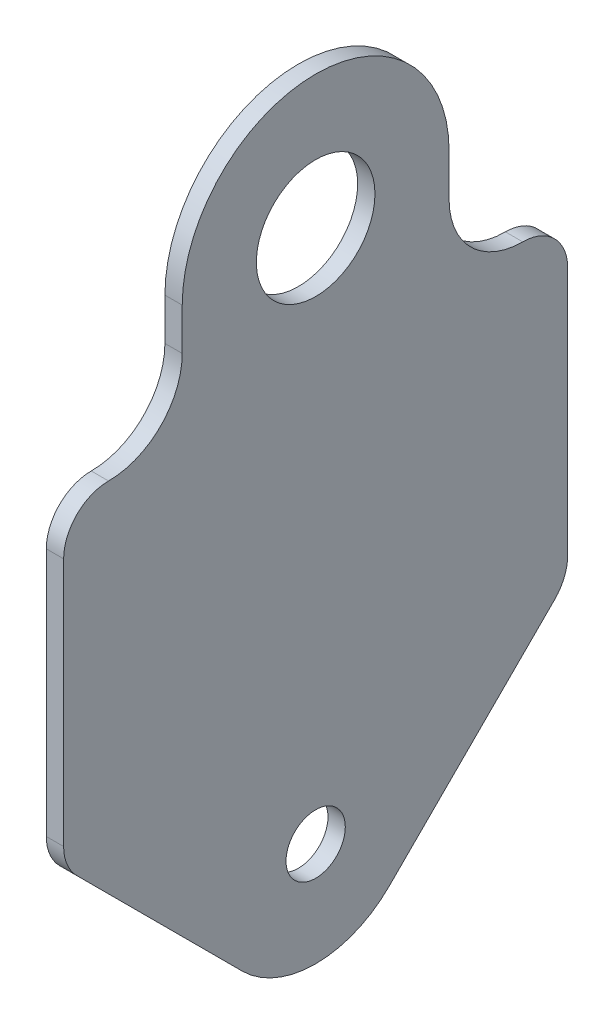
SolidWorks part; units mm, degrees
material "6061-T6 (SS)"
ref_plane "Front" through (0, 0, 0) normal (0, 0, 1) x (1, 0, 0)
ref_plane "Top" through (0, 0, 0) normal (0, 1, 0) x (1, 0, 0)
ref_plane "Right" through (0, 0, 0) normal (1, 0, 0) x (0, 0, -1)
ref_axis "side-side" through (80.9, 0, 0) along (-1, 0, 0)
ref_axis "up-down" through (0, 50, 0) along (0, -1, 0)
ref_axis "front-back" through (0, 0, -80.9) along (0, 0, 1)
sketch "Sketch1" plane through (0, 0, 0) normal (1, 0, 0) x (0, 0, -1)
  line L0 (0, 0) -> (-27.9363, -5.6405) construction
  line L1 (-18, 0) -> (18, 0) construction
  line L2 (-18, 0) -> (-18, -5.6405)
  line L4 (18, 0) -> (18, -5.6405)
  line L6 (-34, -21.6405) -> (-34, -55.2473)
  line L7 (-32.224, -59.535) -> (-9.8995, -81.8595)
  line L8 (0, -71.96) -> (0, -41.7737) construction
  line L9 (34, -21.6405) -> (34, -55.2473)
  line L10 (9.8995, -81.8595) -> (32.224, -59.535)
  line L12 (0, 50) -> (0, -50) construction
  arc A0 (-18, 0) -> (18, 0) centre (0, 0) cw
  circle A1 centre (0, 0) radius 8
  circle A2 centre (0, -71.96) radius 4
  arc A3 (-9.8995, -81.8595) -> (9.8995, -81.8595) centre (0, -71.96) ccw
  circle A4 centre (-27.9363, -5.6405) radius 7.48 construction
  arc A6 (0.5117, 28.4954) -> (-27.9363, -5.6405) centre (0, 0) ccw construction
  arc A8 (-27.9363, -15.5768) -> (-18, -5.6405) centre (-27.9363, -5.6405) ccw
  arc A9 (-27.9363, -15.5768) -> (-34, -21.6405) centre (-27.9363, -21.6405) ccw
  arc A10 (-34, -55.2473) -> (-32.224, -59.535) centre (-27.9363, -55.2473) ccw
  arc A11 (18, -5.6405) -> (27.9363, -15.5768) centre (27.9363, -5.6405) ccw
  arc A12 (27.9363, -15.5768) -> (34, -21.6405) centre (27.9363, -21.6405) cw
  arc A13 (34, -55.2473) -> (32.224, -59.535) centre (27.9363, -55.2473) cw
  circle A14 centre (-29.2625, -43.5) radius 1.3525 construction
  circle A15 centre (-29.2625, -32) radius 1.3525 construction
  dimension "D1" = 16
  dimension "D2" = 10
  dimension "D4" = 8
  dimension "D5" = 28
  dimension "D6" = 10
  dimension "D3" = 28.5
  dimension "D7" = 14.96
  dimension "D8" = 71.96
  dimension "D9" = 101.415
  dimension "D10" = 68
  dimension "D11" = 45
extrude "Boss-Extrude1" add sketch "Sketch1" along normal blind 2.3368
